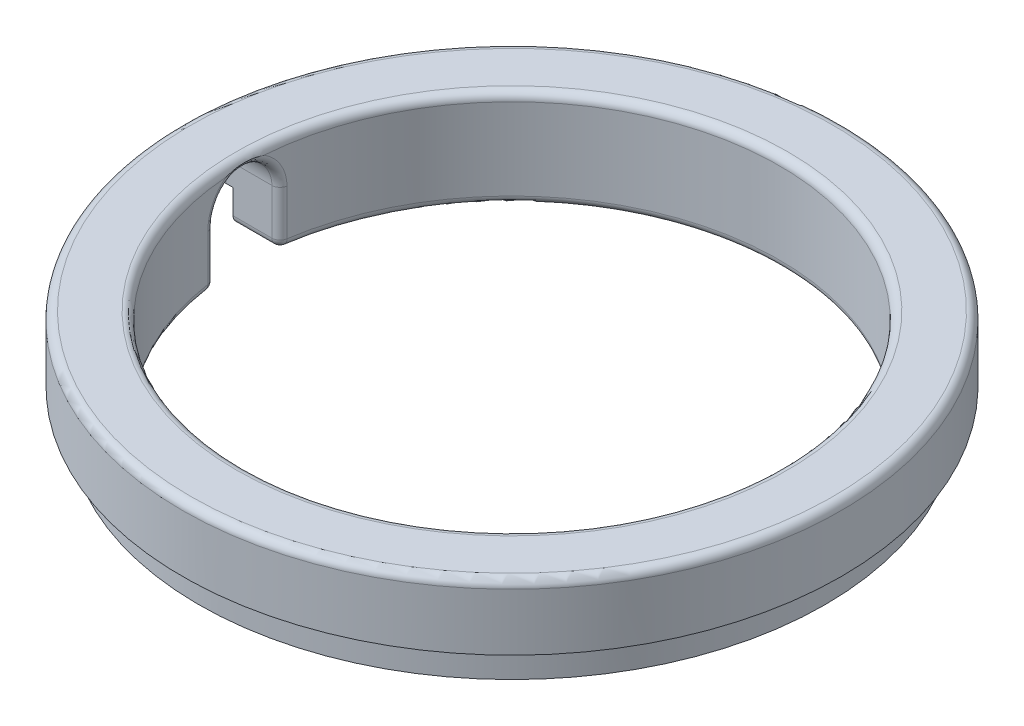
SolidWorks part; units mm, degrees
ref_plane "Ebene vorne" through (0, 0, 0) normal (0, 0, 1) x (1, 0, 0)
ref_plane "Ebene oben" through (0, 0, 0) normal (0, 1, 0) x (1, 0, 0)
ref_plane "Ebene rechts" through (0, 0, 0) normal (1, 0, 0) x (0, 0, -1)
sketch "Skizze1" plane through (0, 0, 0) normal (0, 1, 0) x (1, 0, 0)
  circle A5 centre (0, 0) radius 9.6
  circle A45 centre (0, 0) radius 8.2
  point P0 (0, 0)
  point P124 (0, 0)
extrude "Aufsatz-Linear austragen1" add sketch "Skizze1" along normal blind 1
sketch "Skizze2" plane through (0, 1, 0) normal (0, 1, 0) x (1, 0, 0)
  circle A0 centre (0, 0) radius 8.2
  circle A1 centre (0, 0) radius 10.1
extrude "Aufsatz-Linear austragen2" add sketch "Skizze2" along normal blind 2
sketch "Skizze4" plane through (0, 0, 0) normal (1, 0, 0) x (0, 0, -1)
  line L0 (0, 0) -> (0, 1.65) construction
  line L1 (-1, 0) -> (-1, 1.65)
  line L2 (1, 0) -> (1, 1.65)
  arc A0 (-1, 0) -> (1, 0) centre (0, 0) ccw
  arc A1 (1, 1.65) -> (-1, 1.65) centre (0, 1.65) ccw
  point P3 (0, 0.825)
extrude "Schnitt-Linear austragen1" cut sketch "Skizze4" against normal through all
fillet "Verrundung1" radius 0.25 11 edges at (8.2, 0, 0) (0, 3, 8.2) (0, 3, 10.1) (-10.0504, 1.325, 1) (-10.0994, 2.6435, 0.1134) (-8.1388, 0.825, 1) (-8.1992, 2.6437, 0.1122) (-10.0504, 1.325, -1) (-8.8433, 0, 1) (-8.8433, 0, -1) (-8.1388, 0.825, -1)
